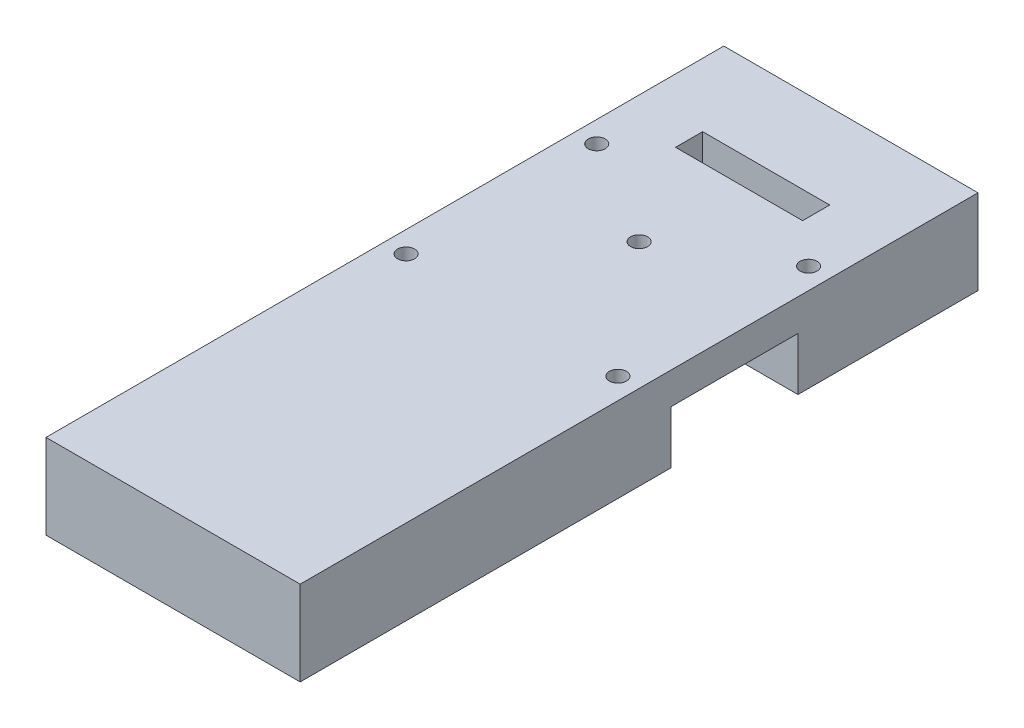
SolidWorks part; units mm, degrees
ref_plane "Front Plane" through (0, 0, 0) normal (0, 0, 1) x (1, 0, 0)
ref_plane "Top Plane" through (0, 0, 0) normal (0, 1, 0) x (1, 0, 0)
ref_plane "Right Plane" through (0, 0, 0) normal (1, 0, 0) x (0, 0, -1)
sketch "Sketch1" plane through (0, 0, 0) normal (0, 1, 0) x (1, 0, 0)
  line L1 (-38.1, -101.6) -> (38.1, -101.6)
  line L2 (-38.1, -101.6) -> (-38.1, 101.6)
  line L3 (-38.1, 101.6) -> (38.1, 101.6)
  line L4 (38.1, -101.6) -> (38.1, 101.6)
  line L5 (-38.1, -101.6) -> (38.1, 101.6) construction
  line L6 (-38.1, 101.6) -> (38.1, -101.6) construction
  point P0 (0, 0)
  dimension "D1" = 76.2
  dimension "D2" = 203.2
extrude "Boss-Extrude1" add sketch "Sketch1" along normal blind 12.7 and the other way blind 12.7
sketch "Sketch2" plane through (0, 0, -101.6) normal (0, 0, -1) x (-1, 0, 0)
  line L1 (-38.1, -12.7) -> (38.1, -12.7) construction
  circle A0 centre (0, -12.7) radius 4.7625
  dimension "D1" = 9.525
extrude "Cut-Extrude1" cut sketch "Sketch2" against normal blind 25.4
ref_plane "Plane1" through (0, -12.7, 0) normal (0, -1, 0) x (-1, 0, 0)
sketch "Sketch3" plane through (0, -12.7, 0) normal (0, -1, 0) x (-1, 0, 0)
  line L0 (4.7625, 76.2) -> (-4.7625, 76.2) construction
  line L1 (-19.05, -96.8375) -> (19.05, -96.8375)
  line L2 (-25.4, -90.4875) -> (-25.4, 9.525)
  line L3 (-22.225, 76.2) -> (22.225, 76.2)
  line L4 (25.4, -90.4875) -> (25.4, 9.525)
  line L5 (22.225, 68.072) -> (-22.225, 68.072)
  line L6 (25.4, 9.525) -> (44.45, 9.525)
  line L7 (25.4, 71.247) -> (25.4, 73.025)
  line L8 (-25.4, 71.247) -> (-25.4, 73.025)
  line L10 (-44.45, 9.525) -> (-25.4, 9.525)
  line L11 (-44.45, 9.525) -> (-44.45, 47.625)
  line L12 (-44.45, 47.625) -> (44.45, 47.625)
  line L13 (44.45, 9.525) -> (44.45, 47.625)
  line L14 (4.7625, 101.6) -> (4.7625, 76.2)
  line L15 (4.7625, 76.2) -> (-4.7625, 76.2)
  line L16 (-4.7625, 76.2) -> (-4.7625, 101.6)
  line L17 (-4.7625, 101.6) -> (-38.1, 101.6)
  line L18 (-38.1, 101.6) -> (-38.1, -101.6)
  line L19 (-38.1, -101.6) -> (38.1, -101.6)
  line L20 (38.1, -101.6) -> (38.1, 101.6)
  line L21 (38.1, 101.6) -> (4.7625, 101.6)
  line L25 (-4.7625, 101.6) -> (-38.1, 101.6) construction
  line L26 (-38.1, 101.6) -> (-38.1, -101.6) construction
  line L27 (-38.1, -101.6) -> (38.1, -101.6) construction
  line L28 (38.1, -101.6) -> (38.1, 101.6) construction
  line L29 (38.1, 101.6) -> (4.7625, 101.6) construction
  arc A0 (-25.4, -90.4875) -> (-19.05, -96.8375) centre (-19.05, -90.4875) ccw
  arc A1 (19.05, -96.8375) -> (25.4, -90.4875) centre (19.05, -90.4875) ccw
  arc A2 (25.4, 73.025) -> (22.225, 76.2) centre (22.225, 73.025) ccw
  arc A3 (-22.225, 76.2) -> (-25.4, 73.025) centre (-22.225, 73.025) ccw
  arc A6 (-22.225, 68.072) -> (-25.4, 71.247) centre (-22.225, 71.247) cw
  arc A7 (22.225, 68.072) -> (25.4, 71.247) centre (22.225, 71.247) ccw
  point P33 (-25.4, 68.072)
  point P36 (25.4, 68.072)
  dimension "D5" = 6.35
  dimension "D6" = 8.128
  dimension "D8" = 19.05
  dimension "D9" = 3.175
  dimension "D2" = 25.4
  dimension "D3" = 25.4
  dimension "D4" = 9.525
  dimension "D7" = 38.1
  dimension "D10" = 53.975
  dimension "D1" = 0
extrude "Cut-Extrude2" cut sketch "Sketch3" against normal blind 15.875
sketch "Sketch5" plane through (0, 0, 0) normal (0, 1, 0) x (1, 0, 0)
  line L0 (4.7625, 76.2) -> (22.225, 76.2) construction
  line L1 (19.05, 76.2) -> (-19.05, 76.2)
  line L2 (19.05, 76.2) -> (19.05, 68.072)
  line L3 (19.05, 68.072) -> (-19.05, 68.072)
  line L4 (-19.05, 76.2) -> (-19.05, 68.072)
  line L5 (0, 0) -> (0, 132.0825) construction
  dimension "D1" = 8.128
  dimension "D2" = 38.1
extrude "Cut-Extrude4" cut sketch "Sketch5" along normal through all
hole_wizard "1/4-20 Tapped Hole1" positions "Sketch8" profile "Sketch7" tap size "1/4-20" standard "ANSI Inch"
sketch "Sketch8" plane through (-11.0345, 12.7, 14.5475) normal (0, -1, 0) x (-1, 0, 0)
  line L0 (11.1905, 90.7475) -> (-6.272, 90.7475) construction
  point P0 (-11.0345, 52.6475)
  dimension "D1" = 38.1
  dimension "D2" = 0
sketch "Sketch7" plane through (0, 12.7, -38.1) normal (1, 0, 0) x (0, 0, 1)
  line L0 (0, 0) -> (0, 20.5838)
  line L1 (0, 20.5838) -> (2.5527, 19.05)
  line L2 (2.5527, 19.05) -> (2.5527, 0)
  line L5 (2.5527, 0) -> (0, 0)
  line L10 (0, 20.5838) -> (-2.5527, 19.05) construction
  line L11 (0, -6.35) -> (0, 107.95) construction
  dimension "Tap Drill Dia." = 5.1054
  dimension "Tap Drill Depth" = 19.05
  dimension "Drill Angle" = 118
cosmetic thread "Hole Thread2" parameters "D1"=9.525, "D2"=6.35
sketch "Sketch9" plane through (0, -12.7, 0) normal (0, -1, 0) x (-1, 0, 0)
  line L0 (38.1, 0) -> (25.4, 0) construction
  line L1 (38.1, 9.525) -> (38.1, -101.6) construction
  line L2 (25.4, -90.4875) -> (25.4, 9.525) construction
  line L3 (25.4, 9.525) -> (38.1, 9.525) construction
  line L4 (38.1, 57.15) -> (25.4, 57.15) construction
  line L5 (38.1, 101.6) -> (38.1, 47.625) construction
  line L6 (38.1, 47.625) -> (-38.1, 47.625) construction
  line L7 (0, 0) -> (0, 53.9724) construction
  circle A0 centre (31.75, 57.15) radius 2.5527
  circle A1 centre (31.75, 0) radius 2.5527
  circle A2 centre (-31.75, 0) radius 2.5527
  circle A3 centre (-31.75, 57.15) radius 2.5527
  dimension "D1" = 9.525
  dimension "D2" = 5.1054
  dimension "D3" = 9.525
extrude "Cut-Extrude5" cut sketch "Sketch9" against normal through all
